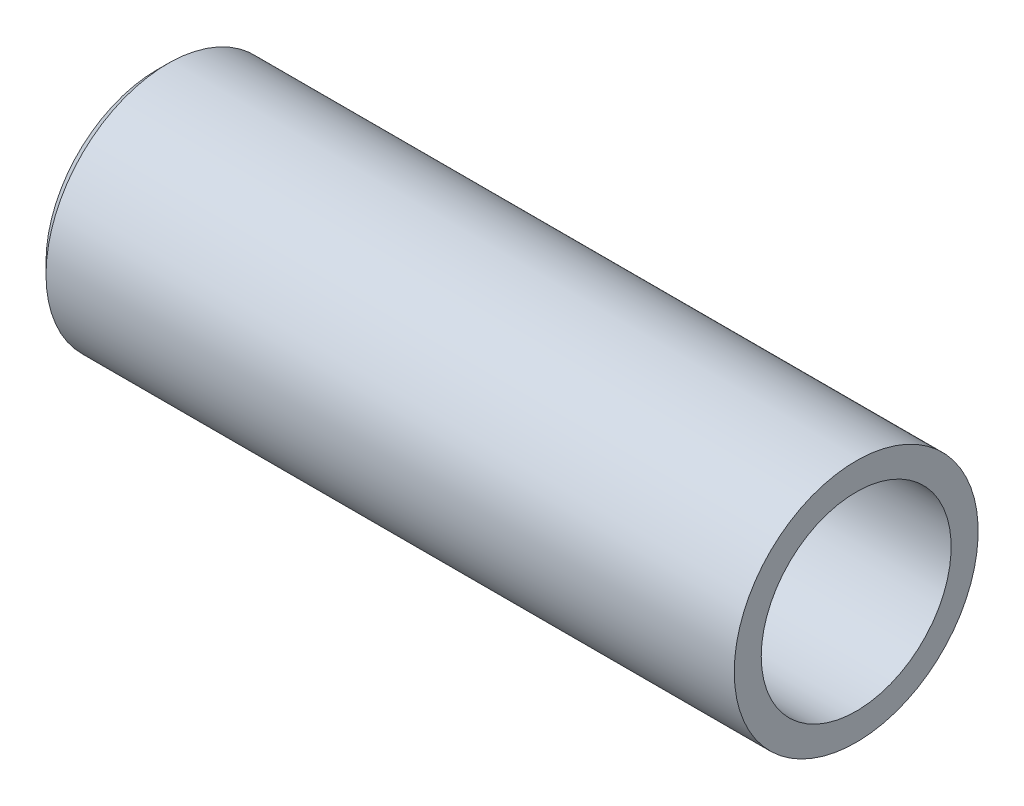
SolidWorks part; units mm, degrees
material "Nylon 6/10"
ref_plane "Front Plane" through (0, 0, 0) normal (0, 0, 1) x (1, 0, 0)
ref_plane "Top Plane" through (0, 0, 0) normal (0, 1, 0) x (1, 0, 0)
ref_plane "Right Plane" through (0, 0, 0) normal (1, 0, 0) x (0, 0, -1)
sketch "Sketch1" plane through (0, 0, 0) normal (0, 0, 1) x (1, 0, 0)
  line L0 (0, 0) -> (22.1407, 0) construction
  line L1 (0.3533, 5.4227) -> (30.9563, 5.4227)
  line L3 (-0.1437, 4.2228) -> (30.9563, 4.2228)
  line L4 (30.9563, 5.4227) -> (30.9563, 4.2228)
  line L5 (30.9563, 11.1125) -> (30.9563, -11.1125) construction
  line L6 (44.1854, 3.9688) -> (-54.7878, 3.9688) construction
  line L7 (-0.1437, -4.1672) -> (-0.1437, 4.1672) construction
  line L8 (-0.1437, 4.2228) -> (-0.1437, 4.9257)
  line L9 (-0.1437, 4.9257) -> (0.3533, 5.4227)
  dimension "D4" = 45
  dimension "D2" = 1.2
  dimension "D1" = 0.254
revolve "Revolve1" add sketch "Sketch1" angle 360 about L0
equation "\"D2@Sketch1\"=1.2mm"
